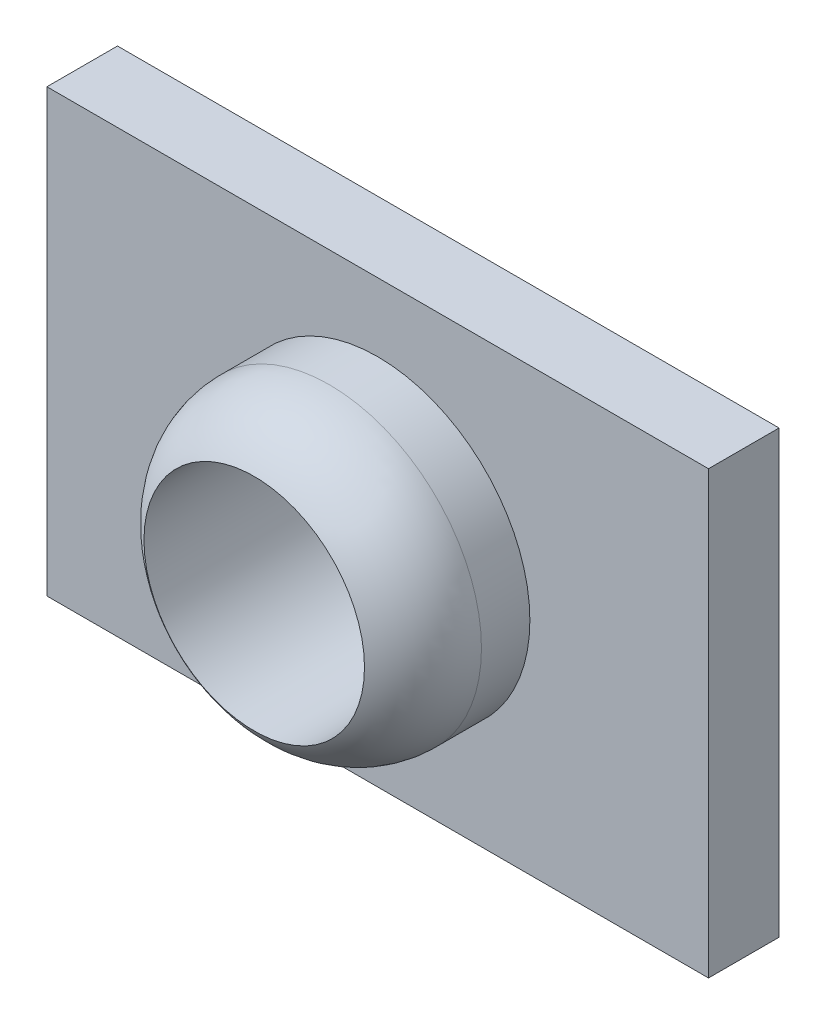
SolidWorks part; units mm, degrees
material "Chrome Stainless Steel"
ref_plane "Front Plane" through (0, 0, 0) normal (0, 0, 1) x (1, 0, 0)
ref_plane "Top Plane" through (0, 0, 0) normal (0, 1, 0) x (1, 0, 0)
ref_plane "Right Plane" through (0, 0, 0) normal (1, 0, 0) x (0, 0, -1)
sketch "Sketch1" plane through (0, 0, 0) normal (0, 0, 1) x (1, 0, 0)
  line L0 (7.5, 0) -> (0, 0) construction
  line L1 (-7.5, -5) -> (7.5, -5)
  line L2 (-7.5, -5) -> (-7.5, 5)
  line L3 (-7.5, 5) -> (7.5, 5)
  line L4 (7.5, -5) -> (7.5, 5)
  line L5 (0, 0) -> (0, 5) construction
  circle A0 centre (0, 0) radius 2.5
  circle A1 centre (0, 0) radius 3.45
  dimension "D1" = 5
  dimension "D2" = 6.9
  dimension "D3" = 7.5
  dimension "D4" = 5
extrude "Boss-Extrude1" add sketch "Sketch1" along normal blind 4.4 contours A1 A0 region at (-3.3524, 0, 0)
extrude "Boss-Extrude2" add sketch "Sketch1<3>" along normal blind 1.6 contours L1 L4 L3 L2 A1 region at (-7.3197, 0, 0)
sketch "Sketch1<3>" plane through (0, 0, 0) normal (0, 0, 1) x (1, 0, 0) same geometry as "Sketch1"
fillet "Fillet1" radius 2 1 edges at (3.45, 0, 4.4)
